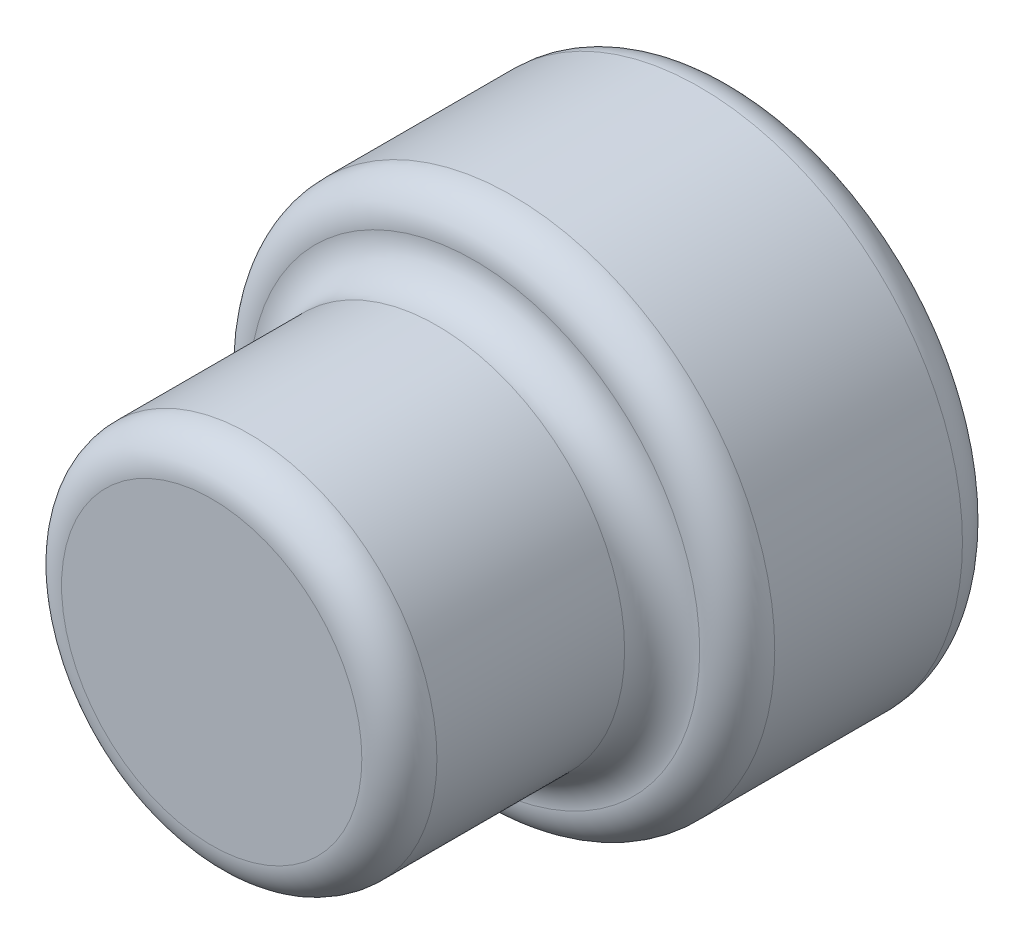
SolidWorks part; units mm, degrees
ref_plane "Front Plane" through (0, 0, 0) normal (0, 0, 1) x (1, 0, 0)
ref_plane "Top Plane" through (0, 0, 0) normal (0, 1, 0) x (1, 0, 0)
ref_plane "Right Plane" through (0, 0, 0) normal (1, 0, 0) x (0, 0, -1)
sketch "Sketch1" plane through (0, 0, 0) normal (0, 0, 1) x (1, 0, 0)
  circle A0 centre (0, 0) radius 7
  dimension "D1" = 14
extrude "Boss-Extrude1" add sketch "Sketch1" along normal blind 7
fillet "Fillet1" radius 1 2 edges at (7, 0, 0) (7, 0, 7)
sketch "Sketch2" plane through (0, 0, 7) normal (0, 0, 1) x (1, 0, 0)
  circle A0 centre (0, 0) radius 5
  dimension "D1" = 10
extrude "Boss-Extrude2" add sketch "Sketch2" along normal blind 7
fillet "Fillet2" radius 1 2 edges at (5, 0, 14) (5, 0, 7)
